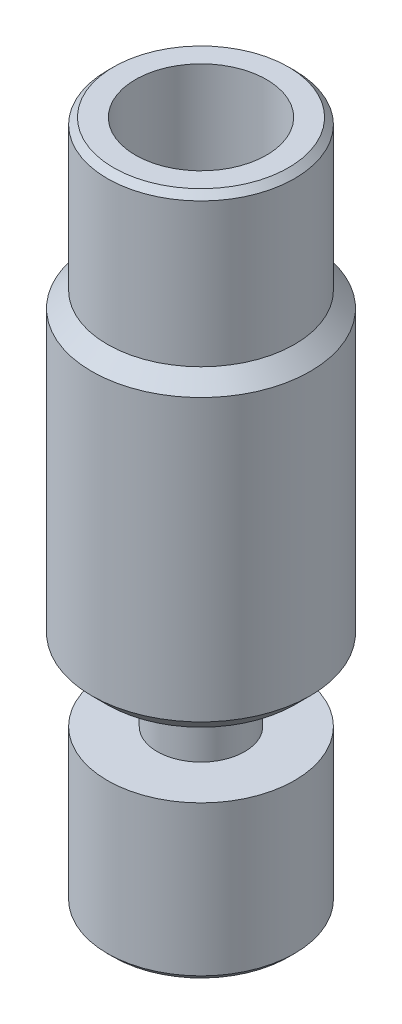
SolidWorks part; units mm, degrees
ref_plane "Спереди" through (0, 0, 0) normal (0, 0, 1) x (1, 0, 0)
ref_plane "Сверху" through (0, 0, 0) normal (0, 1, 0) x (1, 0, 0)
ref_plane "Справа" through (0, 0, 0) normal (1, 0, 0) x (0, 0, -1)
sketch "Эскиз1" plane through (0, 0, 0) normal (1, 0, 0) x (0, 0, -1)
  line L0 (0, 0) -> (0, 37.1488) construction
  line L1 (-1, 21.9) -> (-1, 0)
  line L2 (-1, 0) -> (-3, 0)
  line L3 (-3, 0) -> (-3, 5)
  line L4 (-3, 5) -> (-1.4, 5)
  line L5 (-1.4, 5) -> (-1.4, 7.1)
  line L6 (-1.4, 7.1) -> (-3.5, 7.1)
  line L7 (-3.5, 7.1) -> (-3.5, 17.1)
  line L8 (-3.5, 17.1) -> (-3, 17.1)
  line L9 (-3, 17.1) -> (-3, 21.9)
  line L10 (-3, 21.9) -> (-1, 21.9)
  dimension "D1" = 6
  dimension "D2" = 2
  dimension "D3" = 2.8
  dimension "D4" = 2.1
  dimension "D5" = 7.1
  dimension "D6" = 7
  dimension "D7" = 6
  dimension "D8" = 14.8
  dimension "D9" = 4.8
revolve "Повернуть1" add sketch "Эскиз1" angle 360 about L0
cosmetic thread "Условное изображение резьбы1" parameters "D1"=10, "D2"=5.917
cosmetic thread "Условное изображение резьбы2" parameters "D2"=4.917
hole_wizard "Отверстие1" positions "Эскиз3" profile "Эскиз2" legacy
sketch "Эскиз3" plane through (0, 21.9, 0) normal (0, 1, 0) x (-1, 0, 0)
  point P0 (0, 0)
sketch "Эскиз2" plane through (0, 21.9, 0) normal (1, 0, 0) x (0, 0, 1)
  line L0 (0, 0) -> (0, 6.0618)
  line L1 (0, 6.0618) -> (2.1, 4.8)
  line L2 (2.1, 4.8) -> (2.1, 0)
  line L4 (2.1, 0) -> (0, 0)
  line L6 (0, 6.0618) -> (-2.1, 4.8) construction
  line L7 (0, -4.2442) -> (0, 117.3081) construction
  dimension "Диаметр" = 4.2
  dimension "Глубина" = 4.8
  dimension "Угол заточки сверла" = 118
chamfer "Фаска1" distance 0.2 angle 45 2 edges at (0, 0, -3) (0, 21.9, -3)
chamfer "Фаска2" distance 0.5 angle 45 2 edges at (0, 7.1, -3.5) (0, 17.1, -3.5)
